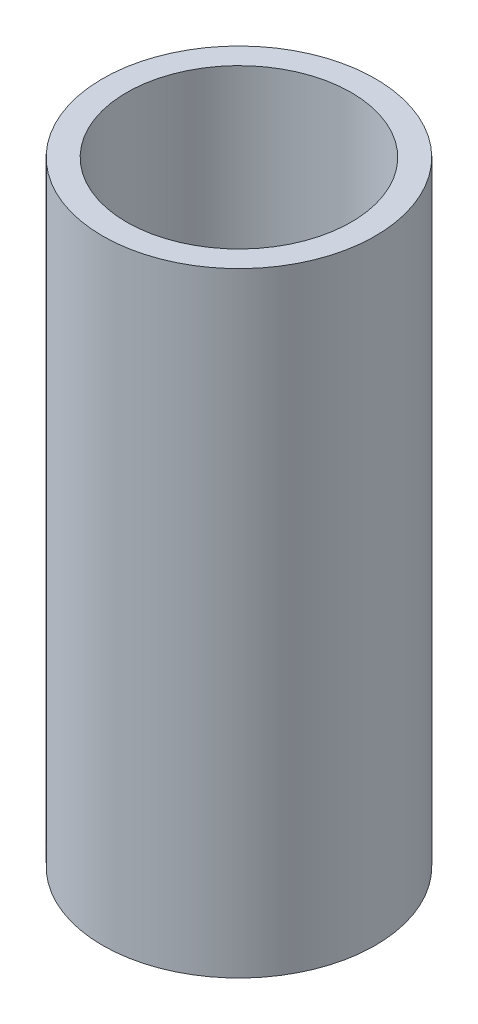
SolidWorks part; units mm, degrees
ref_plane "Front Plane" through (0, 0, 0) normal (0, 0, 1) x (1, 0, 0)
ref_plane "Top Plane" through (0, 0, 0) normal (0, 1, 0) x (1, 0, 0)
ref_plane "Right Plane" through (0, 0, 0) normal (1, 0, 0) x (0, 0, -1)
sketch "Sketch1" plane through (0, 0, 0) normal (0, 1, 0) x (1, 0, 0)
  circle A0 centre (0, 0) radius 37.5
  dimension "SLEEVE_OD" = 75
extrude "Boss-Extrude1" add sketch "Sketch1" along normal blind 168.9806
sketch "Sketch2" plane through (0, 0, 0) normal (0, 1, 0) x (1, 0, 0)
  circle A0 centre (0, 0) radius 30.8902
  dimension "BORE_D" = 61.7805
extrude "Cut-Extrude1" cut sketch "Sketch2" along normal through all
chamfer "Chamfer1" distance 3.8336 angle 50.594 rebuild error yes
